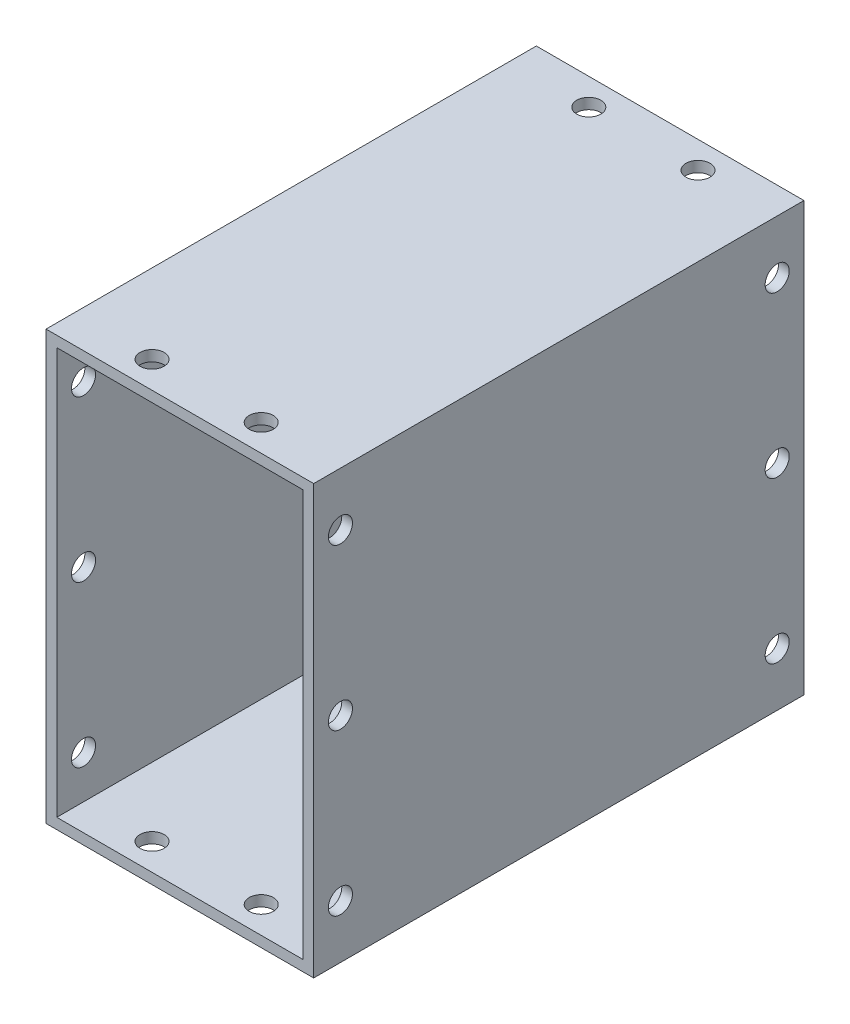
SolidWorks part; units mm, degrees
note: '?' marks a value the reader was unsure of.
material "1.4301 (X5CrNi18-10)"
ref_plane "Front Plane" through (0, 0, 0) normal (0, 0, 1) x (1, 0, 0)
ref_plane "Top Plane" through (0, 0, 0) normal (0, 1, 0) x (1, 0, 0)
ref_plane "Right Plane" through (0, 0, 0) normal (1, 0, 0) x (0, 0, -1)
ref_axis "Axis1" through (0, 0, 187.293) along (0, 0, -1)?
ref_plane "Plane1" through (0, 0, 60) normal (0, 0, 1) x (1, 0, 0)
ref_axis "Elbow" through (0, -45.4288, 181.6) along (0, 1, 0)?
ref_plane "Plane2" through (0, 0, 181.6) normal (0, 0, 1) x (1, 0, 0)
ref_plane "Plane3" through (0, 0, 151.6) normal (0, 0, 1) x (1, 0, 0)
ref_point "Point2"
sketch "Sketch1" plane through (0, 0, 60) normal (0, 0, 1) x (1, 0, 0)
  line L0 (25, 40) -> (-25, 40) construction
  line L1 (-25, 40) -> (25, 40)
  line L2 (-25, 40) -> (-25, -40)
  line L3 (-25, -40) -> (25, -40)
  line L4 (25, 40) -> (25, -40)
  line L5 (-25, 40) -> (25, -40) construction
  line L6 (-25, -40) -> (25, 40) construction
  line L7 (-25, 40) -> (-25, -40) construction
  line L8 (-23, 38) -> (-23, -38)
  line L9 (-23, -38) -> (23, -38)
  line L10 (23, 38) -> (23, -38)
  line L11 (-23, 38) -> (23, 38)
  point P0 (0, 0)
  dimension "D1" = 2
extrude "Boss-Extrude1" add sketch "Sketch1" along normal up to vertex (91.6 mm away)
hole_wizard "M4 Clearance Hole1" positions "3DSketch1" profile "Sketch4" hole size "M4" standard "DIN" end condition up to next
sketch3d "3DSketch1"
  circle A0 centre (-23, -30, 65) radius 1.65 construction
  circle A1 centre (-23, 0, 65) radius 1.65 construction
  circle A2 centre (-23, 30, 65) radius 1.65 construction
  circle A3 centre (-10.2, 38, 65) radius 1.65 construction
  circle A4 centre (10.2, 38, 65) radius 1.65 construction
  circle A5 centre (23, 30, 65) radius 1.65 construction
  circle A6 centre (23, 0, 65) radius 1.65 construction
  circle A7 centre (23, -30, 65) radius 1.65 construction
  circle A8 centre (10.2, -38, 65) radius 1.65 construction
  circle A9 centre (-10.2, -38, 65) radius 1.65 construction
  circle A10 centre (23, -30, 146.6) radius 1.65 construction
  circle A11 centre (23, 0, 146.6) radius 1.65 construction
  circle A12 centre (23, 30, 146.6) radius 1.65 construction
  circle A13 centre (10.2, 38, 146.6) radius 1.65 construction
  circle A14 centre (-10.2, 38, 146.6) radius 1.65 construction
  circle A15 centre (-23, 30, 146.6) radius 1.65 construction
  circle A16 centre (-23, 0, 146.6) radius 1.65 construction
  circle A17 centre (-23, -30, 146.6) radius 1.65 construction
  circle A18 centre (-10.2, -38, 146.6) radius 1.65 construction
  circle A19 centre (10.2, -38, 146.6) radius 1.65 construction
  point P0 (25, 30, 65)
  point P2 (25, 0, 65)
  point P4 (25, -30, 65)
  point P6 (10.2, -40, 65)
  point P8 (-10.2, -40, 65)
  point P10 (-25, -30, 65)
  point P15 (-25, 30, 65)
  point P17 (-25, 0, 65)
  point P19 (10.2, 40, 65)
  point P21 (-10.2, 40, 65)
  point P26 (10.2, 40, 146.6)
  point P28 (-10.2, 40, 146.6)
  point P36 (-10.2, -40, 146.6)
  point P38 (10.2, -40, 146.6)
  point P40 (-25, 30, 146.6)
  point P42 (-25, 0, 146.6)
  point P44 (-25, -30, 146.6)
  point P50 (25, -30, 146.6)
  point P52 (25, 0, 146.6)
  point P54 (25, 30, 146.6)
  point P60 (-24.65, -30, 65)
  point P64 (-24.65, 0, 65)
  point P68 (-24.65, 30, 65)
  point P71 (-10.2, 39.65, 65)
  point P74 (10.2, 39.65, 65)
  point P77 (24.65, 30, 65)
  point P81 (24.65, 0, 65)
  point P85 (24.65, -30, 65)
  point P88 (10.2, -39.65, 65)
  point P92 (-10.2, -39.65, 65)
  point P97 (24.65, -30, 146.6)
  point P101 (24.65, 0, 146.6)
  point P105 (24.65, 30, 146.6)
  point P109 (10.2, 39.65, 146.6)
  point P113 (-10.2, 39.65, 146.6)
  point P116 (-24.65, 30, 146.6)
  point P120 (-24.65, 0, 146.6)
  point P124 (-24.65, -30, 146.6)
  point P128 (-10.2, -39.65, 146.6)
  point P132 (10.2, -39.65, 146.6)
sketch "Sketch4" plane through (25, 30, 65) normal (0, 1, 0) x (0, 0, -1)
  line L0 (0, 0) -> (0, 2)
  line L1 (0, 2) -> (2.25, 2)
  line L2 (2.25, 2) -> (2.25, 0)
  line L5 (2.25, 0) -> (0, 0)
  line L11 (0, -6.35) -> (0, 107.95) construction
  dimension "Thru Hole Dia." = 4.5
  dimension "Thru Hole Depth" = 2
